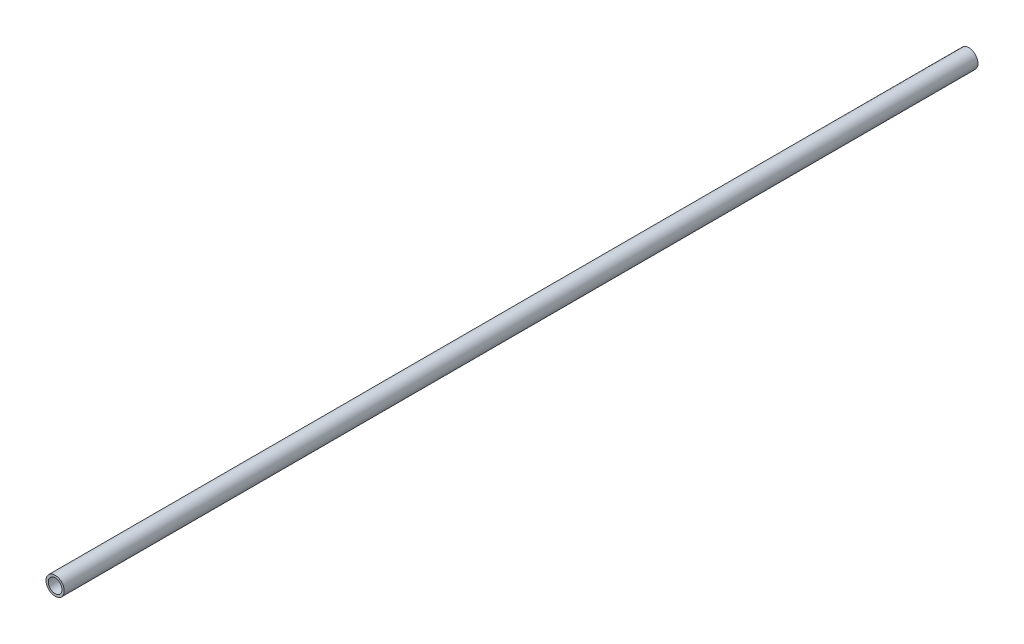
SolidWorks part; units mm, degrees
ref_plane "前视基准面" through (0, 0, 0) normal (0, 0, 1) x (1, 0, 0)
ref_plane "上视基准面" through (0, 0, 0) normal (0, 1, 0) x (1, 0, 0)
ref_plane "右视基准面" through (0, 0, 0) normal (1, 0, 0) x (0, 0, -1)
other "Configuration Table"
sketch "草图1" plane through (0, 0, 0) normal (0, 0, 1) x (1, 0, 0)
  circle A0 centre (0, 0) radius 10
  circle A1 centre (0, 0) radius 7.5
  dimension "D1" = 20
  dimension "D2" = 15
extrude "凸台-拉伸1" add sketch "草图1" along normal blind 1000
ref_axis "基准轴1" through (0, 0, 1000) along (0, 0, -1)
